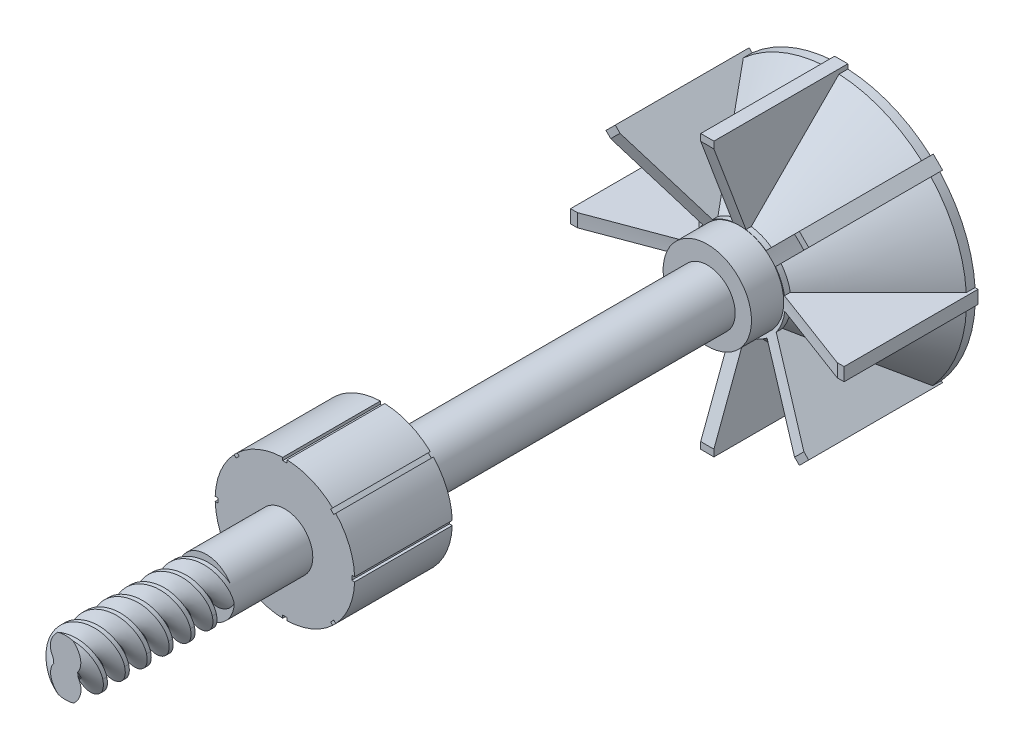
SolidWorks part; units mm, degrees
note: '?' marks a value the reader was unsure of.
material "Chrome Stainless Steel"
ref_plane "Front Plane" through (0, 0, 0) normal (0, 0, 1) x (1, 0, 0)
ref_plane "Top Plane" through (0, 0, 0) normal (0, 1, 0) x (1, 0, 0)
ref_plane "Right Plane" through (0, 0, 0) normal (1, 0, 0) x (0, 0, -1)
ref_axis "Axis1" through (0, 0, -88.99) along (0, 0, 1)?
sketch "Worm-BaseSketch" plane through (0, 0, 0) normal (1, 0, 0) x (0, 0, -1)
  line L0 (-11.1125, 0) -> (11.1125, 0)
  line L1 (11.1125, 0) -> (11.1125, 3.175)
  line L3 (11.1125, 3.175) -> (-11.049, 3.175)
  line L4 (-11.049, 3.175) -> (-11.1125, 3.1115)
  line L5 (-11.1125, 3.1115) -> (-11.1125, 0)
  line L6 (-22.225, 0) -> (22.225, 0) construction
  dimension "Hub Surface" = 11.1125
  dimension "OD" = 3.175
  dimension "Chamfer (3)" = 0.0635
  dimension "Chamfer (4)" = 0.0635
  dimension "Worm Length" = 22.225
revolve "32.0081 Diametral Pitch, Fine Pitch Involute 25 deg" add sketch "Worm-BaseSketch" angle 360 about L6
ref_plane "Plane4" through (0, 0, 12.359) normal (0, 0, 1) x (1, 0, 0)
sketch "Local Files2" plane through (0, 0, 12.359) normal (0, 0, 1) x (1, 0, 0)
  circle A0 centre (0, 0) radius 2.3813
  dimension "D1" = 4.7625
curve "Helix/Spiral1" pitch 4.986 height 24.718 turns 4.9575
sketch "Tooth-Sketch" plane through (0, 0, 0) normal (0, 1, 0) x (1, 0, 0)
  line L0 (3.3843, -11.2389) -> (3.3843, -13.4791)
  line L1 (3.3843, -13.4791) -> (1.5335, -12.5623)
  line L2 (1.3782, -12.312) -> (1.3782, -12.2326)
  line L3 (1.3782, -12.2326) -> (3.3843, -11.2389)
  arc A0 (1.3782, -12.312) -> (1.5335, -12.5623) centre (1.6575, -12.312) ccw
  dimension "D1" = 0.2793
sweep "Tooth-Cut-Sweep RH, PD: 0.8748in" cut profiles "Tooth-Sketch" path "Helix/Spiral1"
pattern_circular "Tooth Pattern,  2" count 2 every 180 about axis through (0, 0, -88.99) along (0, 0, 1) of "Tooth-Cut-Sweep RH, PD: 0.8748in"
ref_plane "Plane5" through (0, 0, -91) normal (0, 0, 1) x (1, 0, 0)
sketch "Sketch4" plane through (0, 0, -91) normal (0, 0, 1) x (1, 0, 0)
  circle A0 centre (0, 0) radius 3.175
  dimension "D1" = 6.35
extrude "Extrude2" add sketch "Sketch4" along normal up to surface (79.8875 mm away) up to face at (0, 0, -11.1125)
sketch "Sketch5" plane through (0, 0, 0) normal (1, 0, 0) x (0, 0, -1)
  line L0 (11.049, 0.1968) -> (91, 0.1968) construction
  line L1 (20.0612, 8.1343) -> (31.1737, 8.1343)
  line L2 (20.0612, 8.1343) -> (20.0612, 0.1968)
  line L3 (20.0612, 0.1968) -> (31.1737, 0.1968)
  line L4 (31.1737, 8.1343) -> (31.1737, 0.1968)
  line L5 (91, 3.4923) -> (91, -3.4923) construction
  dimension "D1" = 15.875
  dimension "D2" = 11.1125
revolve "Revolve1" add sketch "Sketch5" angle 360 about L0
sketch "Sketch6" plane through (0, 0, -20.0612) normal (0, 0, 1) x (1, 0, 0)
  line L0 (0, 0) -> (0, 7.8069) construction
  line L1 (-0.25, 8.3142) -> (0.25, 8.3142)
  line L2 (-0.25, 8.3142) -> (-0.25, 7.8069)
  line L3 (-0.25, 7.8069) -> (0.25, 7.8069)
  line L4 (0.25, 8.3142) -> (0.25, 7.8069)
  dimension "D1" = 0.5
extrude "Cut-Extrude1" cut sketch "Sketch6" against normal up to surface (11.1125 mm away) up to face at (7.9375, 0.1968, -31.1737)
pattern_circular "CirPattern1" count 8 over 360 about axis through (0, 0.1968, 0) along (0, 0, 1) of "Cut-Extrude1"
sketch "Sketch7" plane through (0, 0, 0) normal (1, 0, 0) x (0, 0, -1)
  line L0 (83.3778, 0.1968) -> (83.3778, 15.2622)
  line L2 (83.3778, 15.2622) -> (82.3778, 15.2622)
  line L3 (82.3778, 15.2622) -> (72.3924, 5.2768)
  line L4 (72.3924, 5.2768) -> (68.1378, 5.2768)
  line L5 (68.1378, 5.2768) -> (68.1378, 0.1968)
  line L7 (68.1378, 0.1968) -> (83.3778, 0.1968)
  line L8 (11.049, 0.1968) -> (91, 0.1968) construction
  dimension "D1" = 45
  dimension "D2" = 1
  dimension "D3" = 15.24
  dimension "D4" = 5.08
revolve "Revolve2" add sketch "Sketch7" angle 360 about axis through (0, 0, 22.225) along (0, 0, 1)
sketch "Sketch8" plane through (0, 0, -83.3778) normal (0, 0, -1) x (-1, 0, 0)
  line L0 (0, 15.7622) -> (0, 0) construction
  line L1 (-0.75, 15.7622) -> (0.75, 15.7622)
  line L2 (-0.75, 15.7622) -> (-0.75, 0)
  line L3 (-0.75, 0) -> (0.75, 0)
  line L4 (0.75, 15.7622) -> (0.75, 0)
  circle A0 centre (0, 0) radius 15.2622 construction
  dimension "D1" = 1.5
  dimension "D2" = 0.5
extrude "Extrude3" add sketch "Sketch8" against normal up to surface (15.24 mm away) up to face at (-5.2768, 0, -68.1378)
pattern_circular "CirPattern2" count 8 over 360 about axis through (0, 0.1968, 0) along (0, 0, 1) of "Extrude3"
sketch "Sketch9" plane through (0, 0, 0) normal (1, 0, 0) x (0, 0, -1)
  line L0 (71.8069, 5.2233) -> (68.1378, 15.0009)
  line L2 (68.1378, 5.2233) -> (68.1378, 15.7622) construction
  line L3 (68.1378, 15.0009) -> (65.6301, 15.0009)
  line L4 (65.6301, 15.0009) -> (65.6301, 5.2233)
  line L5 (72.3924, 5.2233) -> (68.1378, 5.2233) construction
  line L6 (65.6301, 5.2233) -> (71.8069, 5.2233)
revolve "Cut-Revolve1" cut sketch "Sketch9" angle 360 about axis through (0, 0.1968, -11.049) along (0, 0, -1)
sketch "Sketch11" plane through (0, 0, 11.1125) normal (0, 0, 1) x (1, 0, 0)
  circle A0 centre (0, 0) radius 2.3813
  dimension "D1" = 4.7625
surface "Surface-Extrude1" sketch "Sketch11" parameters "D1"=22.018
chamfer "Chamfer1" distance 0.5 angle 45 1 edges at (3.175, 0, -91)
sketch "Sketch12" plane through (0, 0, 0) normal (0, 1, 0) x (1, 0, 0)
  line L0 (-17.379, -4.8875) -> (19.6295, -4.8875)
  dimension "D1" = 16
extrude "Cut-Extrude2" cut sketch "Sketch12" against normal through all and the other way through all flip side to cut
